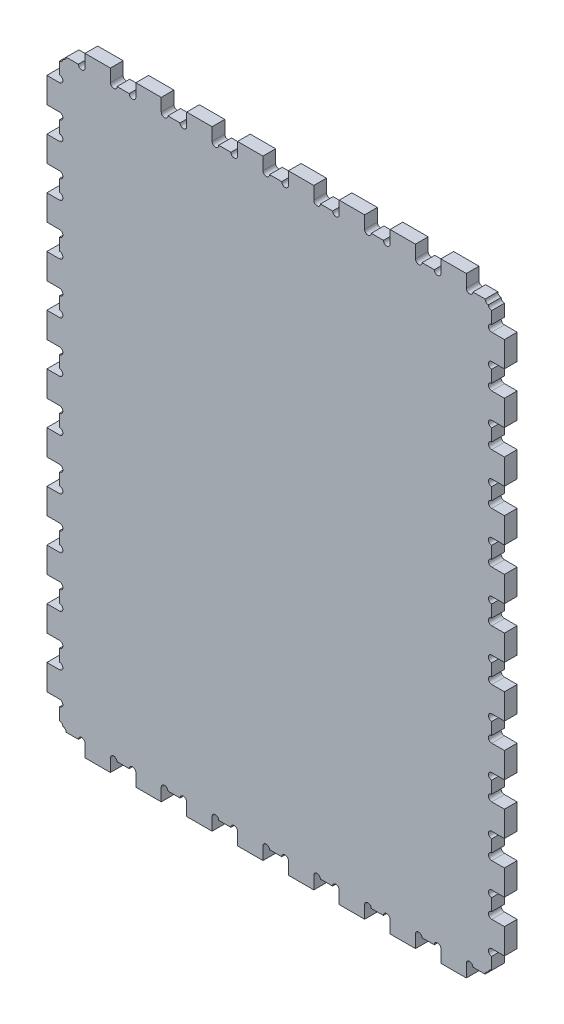
SolidWorks part; units mm, degrees
ref_plane "Front Plane" through (0, 0, 0) normal (0, 0, 1) x (1, 0, 0)
ref_plane "Top Plane" through (0, 0, 0) normal (0, 1, 0) x (1, 0, 0)
ref_plane "Right Plane" through (0, 0, 0) normal (1, 0, 0) x (0, 0, -1)
sketch "Sketch1" plane through (0, 0, 0) normal (0, 0, 1) x (1, 0, 0)
  line L1 (228.6, -304.8) -> (-228.6, -304.8)
  line L2 (228.6, -304.8) -> (228.6, 304.8)
  line L3 (228.6, 304.8) -> (-228.6, 304.8)
  line L4 (-228.6, -304.8) -> (-228.6, 304.8)
  line L5 (228.6, -304.8) -> (-228.6, 304.8) construction
  line L6 (228.6, 304.8) -> (-228.6, -304.8) construction
  line L9 (-203.2, 304.8) -> (-228.6, 304.8) construction
  point P0 (0, 0)
  dimension "D1" = 457.2
  dimension "D2" = 609.6
extrude "Boss-Extrude1" add sketch "Sketch1" along normal blind 12.7
sketch "Sketch2" plane through (0, 0, 12.7) normal (0, 0, 1) x (1, 0, 0)
  line L0 (228.6, 304.8) -> (-228.6, 304.8) construction
  line L1 (-215.9, 292.1) -> (-228.6, 292.1) construction
  line L2 (-215.9, 304.8) -> (-190.5, 304.8)
  line L3 (-215.9, 304.8) -> (-215.9, 292.1)
  line L4 (-215.9, 292.1) -> (-190.5, 292.1)
  line L5 (-190.5, 304.8) -> (-190.5, 292.1)
  line L6 (-228.6, 304.8) -> (-228.6, -304.8) construction
  circle A0 centre (-212.598, 292.1) radius 3.302
  circle A1 centre (-193.802, 292.1) radius 3.302
  line M10 (228.6, 304.8) -> (-228.6, 304.8)
  dimension "D4" = 6.604
  dimension "D5" = 6.604
  dimension "D1" = 25.4
  dimension "D2" = 12.7
  dimension "D3" = 12.7
extrude "Cut-Extrude1" cut sketch "Sketch2" against normal through all contours A1 L5 L3 A0 L4 M10 | L4 A0 | L4 A0 | L4 A1 | L4 A1 region at (-203.2, 299.0379, 12.7) region at (-212.598, 293.5014, 12.7) region at (-212.598, 290.6986, 12.7) region at (-193.802, 290.6986, 12.7) region at (-193.802, 293.5014, 12.7)
pattern_linear "LPattern1" count 9 spacing 50.8 along (1, 0, 0) of "Cut-Extrude1"
sketch "Sketch6" plane through (0, 0, 12.7) normal (0, 0, 1) x (1, 0, 0)
  line L1 (-228.6, 304.8) -> (-215.9, 304.8)
  line L2 (-228.6, 304.8) -> (-228.6, 292.1)
  line L3 (-228.6, 292.1) -> (-215.9, 292.1)
  line L4 (-215.9, 304.8) -> (-215.9, 292.1)
extrude "Cut-Extrude4" cut sketch "Sketch6" against normal through all
sketch "Sketch3" plane through (0, 0, 12.7) normal (0, 0, 1) x (1, 0, 0)
  line L0 (-228.6, 292.1) -> (-228.6, -304.8) construction
  line L1 (-228.6, 292.1) -> (-215.9, 292.1)
  line L2 (-228.6, 292.1) -> (-228.6, 266.7)
  line L3 (-228.6, 266.7) -> (-215.9, 266.7)
  line L4 (-215.9, 292.1) -> (-215.9, 266.7)
  line L5 (-215.9, 292.1) -> (-182.9158, 292.1) construction
  line L6 (-182.9158, 292.1) -> (-182.9158, 304.8) construction
  line L8 (-165.1, 304.8) -> (-190.5, 304.8) construction
  circle A0 centre (-215.9, 288.798) radius 3.302
  circle A1 centre (-215.9, 270.002) radius 3.302
  dimension "D3" = 6.604
  dimension "D4" = 6.604
  dimension "D1" = 25.4
  dimension "D2" = 12.7
  dimension "D5" = 12.7
extrude "Cut-Extrude2" cut sketch "Sketch3" against normal through all contours A1 L4 A0 L1 L2 L3 | L4 A0 | L4 A0 | L4 A1 | L4 A1 region at (-222.8379, 279.4, 12.7) region at (-214.4986, 288.798, 12.7) region at (-217.3014, 288.798, 12.7) region at (-217.3014, 270.002, 12.7) region at (-214.4986, 270.002, 12.7)
pattern_linear "LPattern2" count 12 spacing 50.8 along (0, -1, 0) of "Cut-Extrude2"
ref_plane "Plane1" through (0, 0, 0) normal (1, 0, 0) x (0, 0, -1)
ref_plane "Plane2" through (0, 0, 0) normal (0, 1, 0) x (1, 0, 0)
mirror "Mirror6" about plane through (0, 0, 0) normal (1, 0, 0) of "Cut-Extrude4"
mirror "Mirror7" about plane through (0, 0, 0) normal (0, 1, 0) of "Mirror6", "Cut-Extrude4"
mirror "Mirror1" about plane through (0, 0, 0) normal (1, 0, 0) of "LPattern2"
mirror "Mirror2" about plane through (0, 0, 0) normal (0, 1, 0) of "LPattern1"
